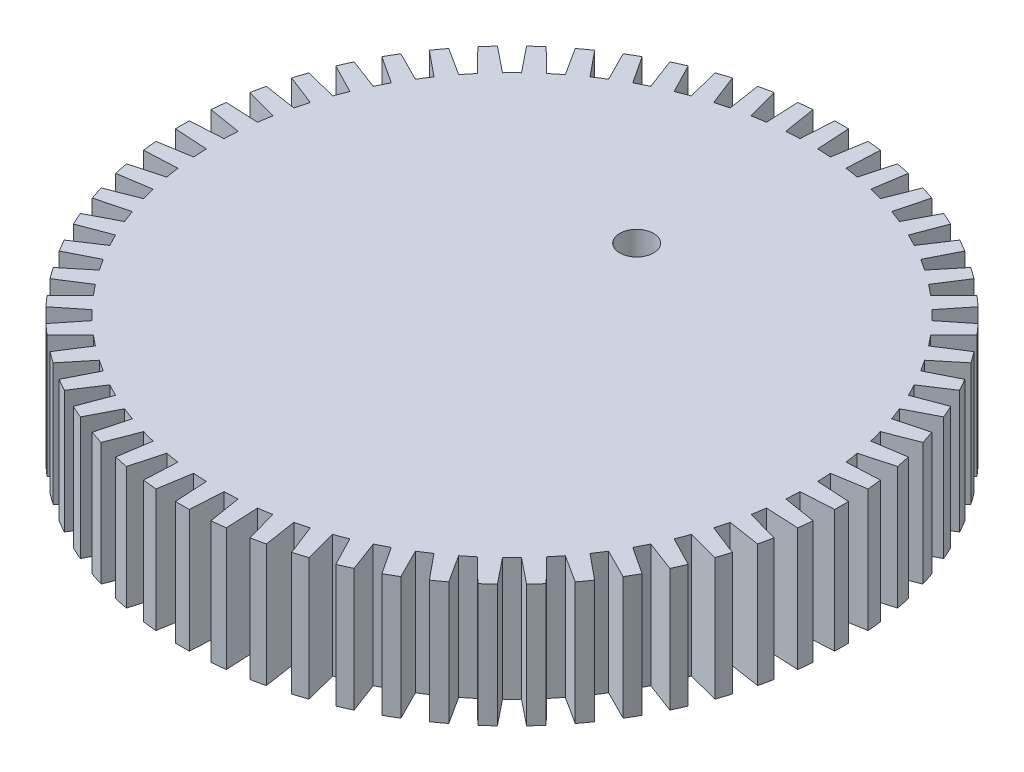
SolidWorks part; units mm, degrees
ref_plane "Front Plane" through (0, 0, 0) normal (0, 0, 1) x (1, 0, 0)
ref_plane "Top Plane" through (0, 0, 0) normal (0, 1, 0) x (1, 0, 0)
ref_plane "Right Plane" through (0, 0, 0) normal (1, 0, 0) x (0, 0, -1)
sketch "Sketch1" plane through (0, 0, 0) normal (0, 1, 0) x (1, 0, 0)
  circle A0 centre (0, 0) radius 30.25
  dimension "D1" = 60.5
extrude "Boss-Extrude2" add sketch "Sketch1" along normal blind 12.5
ref_axis "Axis1" through (0, 12.5, 0) along (0, -1, 0)
sketch "Sketch5" plane through (0, 12.5, 0) normal (0, 1, 0) x (1, 0, 0)
  line L0 (0, 0) -> (0, 30.25) construction
  line L1 (0.9, 30.2366) -> (0.7077, 33.576)
  line L2 (0, 0) -> (0.9, 30.2366) construction
  line L3 (0.9, 30.2366) -> (1.0543, 35.4193) construction
  line L4 (0, 30.25) -> (0, 33.7071) construction
  line L5 (-0.9, 30.2366) -> (-0.7077, 33.576)
  circle A0 centre (0, 0) radius 30.25 construction
  arc A1 (0.9, 30.2366) -> (-0.9, 30.2366) centre (0, 0) ccw
  arc A2 (0.7077, 33.576) -> (-0.7077, 33.576) centre (0, 0) ccw
  dimension "D1" = 355
  dimension "D2" = 1.8
extrude "Boss-Extrude3" add sketch "Sketch5" against normal offset from surface (12.5 mm away) 12.5 up to face at (0, 12.5, 30.25)
pattern_circular "CirPattern1" count 60 over 360 about axis through (0, 12.5, 0) along (0, -1, 0) of "Boss-Extrude3"
sketch "Sketch6" plane through (0, 12.5, 0) normal (0, 1, 0) x (1, 0, 0)
  line L0 (0, 0) -> (0, 12.7) construction
  dimension "D1" = 12.7
hole_wizard "#8-32 Tapped Hole1" positions "Sketch8" profile "Sketch7" tap size "#8-32" standard "ANSI Inch"
sketch "Sketch8" plane through (0, 12.5, 0) normal (0, 1, 0) x (1, 0, 0)
  point P0 (0, 12.7)
sketch "Sketch7" plane through (0, 12.5, -12.7) normal (1, 0, 0) x (0, 0, 1)
  line L0 (0, 0) -> (0, 11.0378)
  line L1 (0, 11.0378) -> (1.7272, 10)
  line L2 (1.7272, 10) -> (1.7272, 0)
  line L5 (1.7272, 0) -> (0, 0)
  line L10 (0, 11.0378) -> (-1.7272, 10) construction
  line L11 (0, -6.35) -> (0, 107.95) construction
  dimension "Tap Drill Dia." = 3.4544
  dimension "Tap Drill Depth" = 10
  dimension "Drill Angle" = 118
cosmetic thread "Hole Thread1" parameters "D1"=10, "D2"=4.1656
